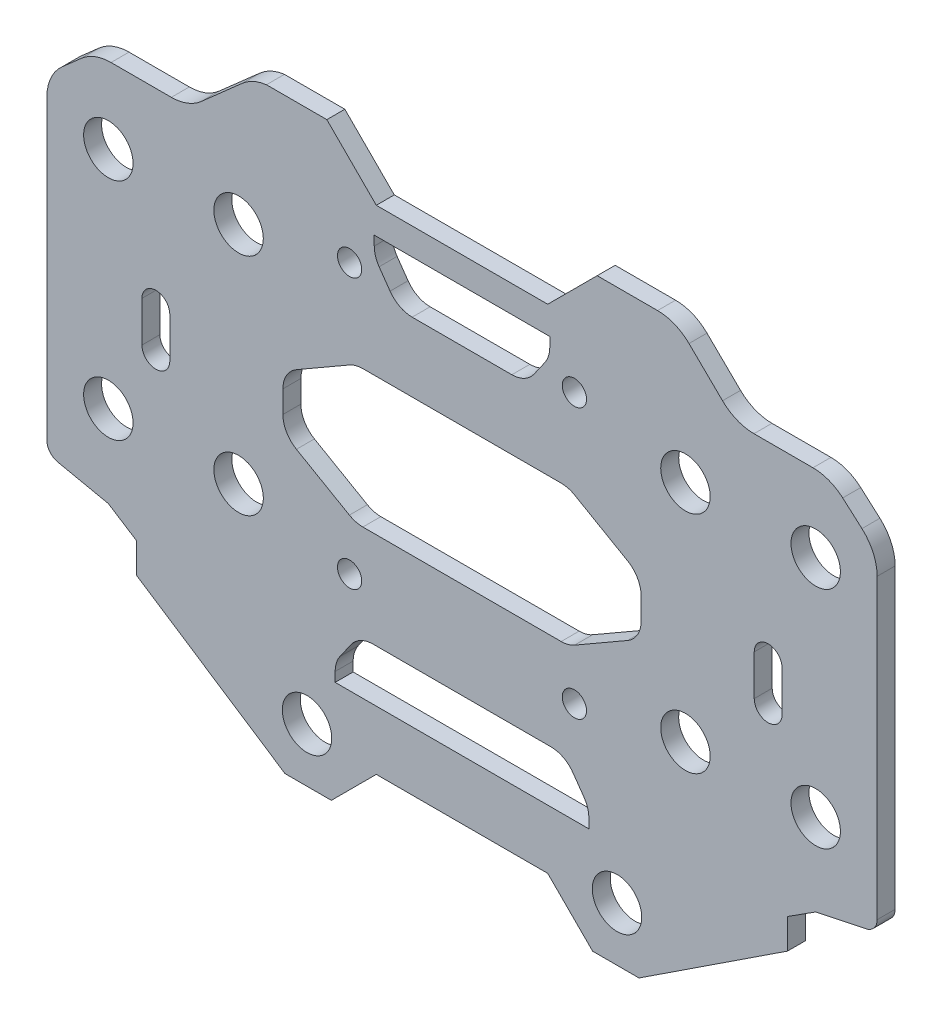
SolidWorks part; units mm, degrees
material "PPS"
ref_plane "前视基准面" through (0, 0, 0) normal (0, 0, 1) x (1, 0, 0)
ref_plane "上视基准面" through (0, 0, 0) normal (0, 1, 0) x (1, 0, 0)
ref_plane "右视基准面" through (0, 0, 0) normal (1, 0, 0) x (0, 0, -1)
sketch "主结构参考" plane through (0, 0, 0) normal (0, 0, 1) x (1, 0, 0)
  line L257 (0, -1000) -> (0, 49000) construction
  line L346 (0, 0) -> (635.1265, 0) construction
  line L351 (-46.1708, 93.9243) -> (-46.1708, 145) construction
  line L358 (-27.9426, 92.9426) -> (-32.5, 97.5) construction
  line L394 (-24.4478, 142.8678) -> (-29.0158, 138.8343)
  line L411 (-32.3253, 137.5823) -> (-39.0335, 137.5823)
  line L414 (-42.3429, 136.3303) -> (-44.4803, 134.4431)
  line L445 (-46.1708, 130.695) -> (-46.1708, 97.6208)
  line L472 (42.3429, 136.3303) -> (44.4803, 134.4431)
  line L494 (46.1729, 155.4291) -> (33.7932, 145.5483) construction
  line L496 (32.4724, 137.5823) -> (39.0335, 137.5823)
  line L497 (25.2455, 142.6568) -> (28.9763, 139.0078)
  line L498 (27.9426, 92.9426) -> (32.5, 97.5) construction
  line L501 (-46.2756, 154.6927) -> (-33.8959, 144.8119) construction
  line L595 (-39.3354, 129.0823) -> (-39.3354, 104.0823) construction
  line L626 (-31.6538, 83.28) -> (-46.1708, 93.9243) construction
  line L628 (-39.3354, 116.5823) -> (0, 116.5823) construction
  line L629 (-15.0322, 144.0823) -> (-9.5322, 138.5823)
  line L630 (-9.5322, 138.5823) -> (9.5322, 138.5823)
  line L631 (15.0322, 144.0823) -> (9.5322, 138.5823)
  line L633 (-21.7494, 144.0823) -> (-15.0322, 144.0823)
  line L635 (15.0322, 144.0823) -> (21.7494, 144.0823)
  line L641 (-9.5322, 83.7633) -> (9.5322, 83.7633)
  line L643 (-9.5322, 83.7633) -> (-14.5322, 78.7633)
  line L644 (30.4418, 78.7633) -> (14.5322, 78.7633) construction
  line L645 (9.5322, 83.7633) -> (14.5322, 78.7633)
  line L646 (11.4529, 96.1323) -> (-11.4529, 96.1323)
  line L647 (-11.4529, 96.1323) -> (-14.109, 92.339)
  line L648 (-14.109, 92.339) -> (-14.109, 90.339)
  line L649 (-14.109, 90.339) -> (14.109, 90.339)
  line L652 (14.109, 92.339) -> (14.109, 90.339)
  line L653 (11.4529, 96.1323) -> (14.109, 92.339)
  line L666 (-35.6, 116.5823) -> (-35.6, 112.0823)
  line L668 (-32.5, 116.5823) -> (-32.5, 112.0823)
  line L670 (35.6, 116.5823) -> (35.6, 112.0823)
  line L671 (32.5, 116.5823) -> (32.5, 112.0823)
  line L681 (-19.6882, 78.7633) -> (-14.5322, 78.7633)
  line L686 (14.5322, 78.7633) -> (19.6882, 78.7633)
  line L687 (-44.9631, 96.1323) -> (-39.3354, 94.9475)
  line L688 (-39.3354, 94.9475) -> (-36.2, 92.9426)
  line L691 (-36.2, 92.9426) -> (-36.2, 89.6081)
  line L692 (-36.2, 89.6081) -> (-19.6882, 78.7633)
  line L693 (36.2, 89.6081) -> (19.6882, 78.7633)
  line L694 (36.2, 92.9426) -> (36.2, 89.6081)
  line L695 (39.3354, 94.9475) -> (36.2, 92.9426)
  line L696 (44.9631, 96.1323) -> (39.3354, 94.9475)
  line L697 (46.1708, 130.695) -> (46.1708, 97.6208)
  line L700 (-19.9188, 111.5033) -> (-11.83, 106.844)
  line L701 (-11.83, 106.844) -> (11.83, 106.844)
  line L706 (19.9188, 111.5033) -> (11.83, 106.844)
  line L709 (-7.1054, 129.7982) -> (7.1054, 129.7982)
  line L710 (7.1054, 129.7982) -> (9.7615, 133.5915)
  line L711 (9.7615, 133.5915) -> (9.7615, 135.5915)
  line L712 (9.7615, 135.5915) -> (-9.7615, 135.5915)
  line L713 (-9.7615, 133.5915) -> (-9.7615, 135.5915)
  line L714 (-7.1054, 129.7982) -> (-9.7615, 133.5915)
  line L715 (-13.3043, 114.4722) -> (9.7615, 114.4722) construction
  line L717 (19.9188, 111.5033) -> (19.9188, 117.4411)
  line L719 (-19.9188, 111.5033) -> (-19.9188, 117.4411)
  line L720 (19.9188, 117.4411) -> (11.83, 122.1004)
  line L721 (-19.9188, 117.4411) -> (-11.83, 122.1004)
  line L722 (-11.83, 122.1004) -> (11.83, 122.1004)
  circle A384 centre (39.3354, 129.0823) radius 2.75
  circle A385 centre (39.3354, 104.0823) radius 2.75
  circle A390 centre (17.238, 84.7633) radius 2.75
  circle A420 centre (-17.238, 84.7633) radius 2.75
  circle A421 centre (-39.3354, 104.0823) radius 2.75
  circle A422 centre (-39.3354, 129.0823) radius 2.75
  arc A453 (32.7926, 143.0294) -> (32.5, 97.5) centre (-120.6696, 121.25) cw construction
  arc A454 (-32.8936, 142.3057) -> (-32.5, 97.5) centre (120.6696, 121.25) ccw construction
  arc A455 (-27.9426, 92.9426) -> (27.9426, 92.9426) centre (0, 290.981) ccw construction
  arc A456 (33.7932, 145.5483) -> (32.7926, 143.0294) centre (35.4973, 143.4132) ccw construction
  arc A457 (-32.8936, 142.3057) -> (-33.8959, 144.8119) centre (-35.6, 142.6768) ccw construction
  circle A463 centre (24.85, 129.0823) radius 2.75
  circle A464 centre (-24.85, 129.0823) radius 2.75
  circle A465 centre (-24.85, 104.0823) radius 2.75
  circle A466 centre (24.85, 104.0823) radius 2.75
  circle A467 centre (12.5, 131.5823) radius 1.35
  circle A468 centre (-12.5, 131.5823) radius 1.35
  circle A469 centre (-12.5, 101.5823) radius 1.35
  circle A470 centre (12.5, 101.5823) radius 1.35
  arc A473 (-44.4803, 134.4431) -> (-46.1708, 130.695) centre (-41.1708, 130.695) ccw
  arc A474 (-39.0335, 137.5823) -> (-42.3429, 136.3303) centre (-39.0335, 132.5823) ccw
  arc A475 (46.1708, 130.695) -> (44.4803, 134.4431) centre (41.1708, 130.695) ccw
  arc A476 (42.3429, 136.3303) -> (39.0335, 137.5823) centre (39.0335, 132.5823) ccw
  arc A477 (32.4724, 137.5823) -> (28.9763, 139.0078) centre (32.4724, 142.5823) cw
  arc A478 (-29.0158, 138.8343) -> (-32.3253, 137.5823) centre (-32.3253, 142.5823) cw
  arc A479 (25.2455, 142.6568) -> (21.7494, 144.0823) centre (21.7494, 139.0823) ccw
  arc A480 (-21.7494, 144.0823) -> (-24.4478, 142.8678) centre (-21.1384, 139.1198) ccw
  arc A481 (-35.6, 116.5823) -> (-32.5, 116.5823) centre (-34.05, 116.5823) cw
  arc A484 (-35.6, 112.0823) -> (-32.5, 112.0823) centre (-34.05, 112.0823) ccw
  arc A486 (35.6, 116.5823) -> (32.5, 116.5823) centre (34.05, 116.5823) ccw
  arc A487 (35.6, 112.0823) -> (32.5, 112.0823) centre (34.05, 112.0823) cw
  arc A490 (-46.1708, 97.6208) -> (-44.9631, 96.1323) centre (-44.6497, 97.6208) ccw
  arc A491 (46.1708, 97.6208) -> (44.9631, 96.1323) centre (44.6497, 97.6208) cw
  point P15 (0, 78.5133)
  point P46 (-46.1708, 132.9503)
  point P50 (-40.925, 137.5823)
  point P53 (46.1708, 132.9503)
  point P56 (40.925, 137.5823)
  point P59 (30.4337, 137.5823)
  point P62 (-30.4337, 137.5823)
  point P65 (23.8205, 144.5823)
  point P69 (-23.8205, 144.5823)
  point P76 (0, 138.5823)
  point P90 (0, 90.339)
  point P92 (0, 96.1323)
  point P110 (18.9567, 119.8323)
  point P118 (0.085, 119.8323)
  point P120 (0.2293, 125.6256)
  point P121 (0, 106.844)
  point P123 (-35.6, 89.214)
  point P124 (6.2431, 127.445)
  point P133 (0, 135.5915)
  point P136 (0, 129.7982)
  point P144 (19.9188, 114.4722)
  point P151 (-19.9188, 114.4722)
  point P152 (-36.0936, 87.9203)
  point P153 (-39.3354, 94.9475)
  point P154 (-36.2, 92.9426)
  point P158 (0, 0)
  point P160 (22.4198, 124.6139)
  dimension "D1" = 84.7633
  dimension "D2" = 17.238
  dimension "D5" = 44.319
  dimension "D6" = 19.319
  dimension "D7" = 22.0974
  dimension "D8" = 22.0974
  dimension "D9" = 6.5
  dimension "D11" = 46.1708
  dimension "D15" = 33.5
  dimension "D17" = 6
  dimension "D23" = 30
  dimension "D38" = 5.5
  dimension "D39" = 155
  dimension "D40" = 200
  dimension "D20" = 5.5
  dimension "D21" = 2.7
  dimension "D22" = 12.5
  dimension "D27" = 135
  dimension "D31" = 1.55
  dimension "D10" = 138.556
  dimension "D12" = 31.6538
  dimension "D13" = 93.9243
  dimension "D14" = 83.28
  dimension "D16" = 5.5
  dimension "D18" = 24.85
  dimension "D19" = 12.5
  dimension "D25" = 5
  dimension "D26" = 135
  dimension "D28" = 125
  dimension "D29" = 2
  dimension "D30" = 20.45
  dimension "D32" = 32.5
  dimension "D33" = 4.5
extrude "凸台-拉伸1" add sketch "主结构参考" along normal blind 2
fillet "圆角1" radius 3 16 edges at (-9.7615, 133.5915, 1) (9.7615, 133.5915, 1) (7.1054, 129.7982, 1) (-7.1054, 129.7982, 1) (14.109, 92.339, 1) (-14.109, 92.339, 1) (11.4529, 96.1323, 1) (-11.4529, 96.1323, 1) (11.83, 106.844, 1) (19.9188, 111.5033, 1) (-11.83, 106.844, 1) (-19.9188, 111.5033, 1) (19.9188, 117.4411, 1) (11.83, 122.1004, 1) (-19.9188, 117.4411, 1) (-11.83, 122.1004, 1)
